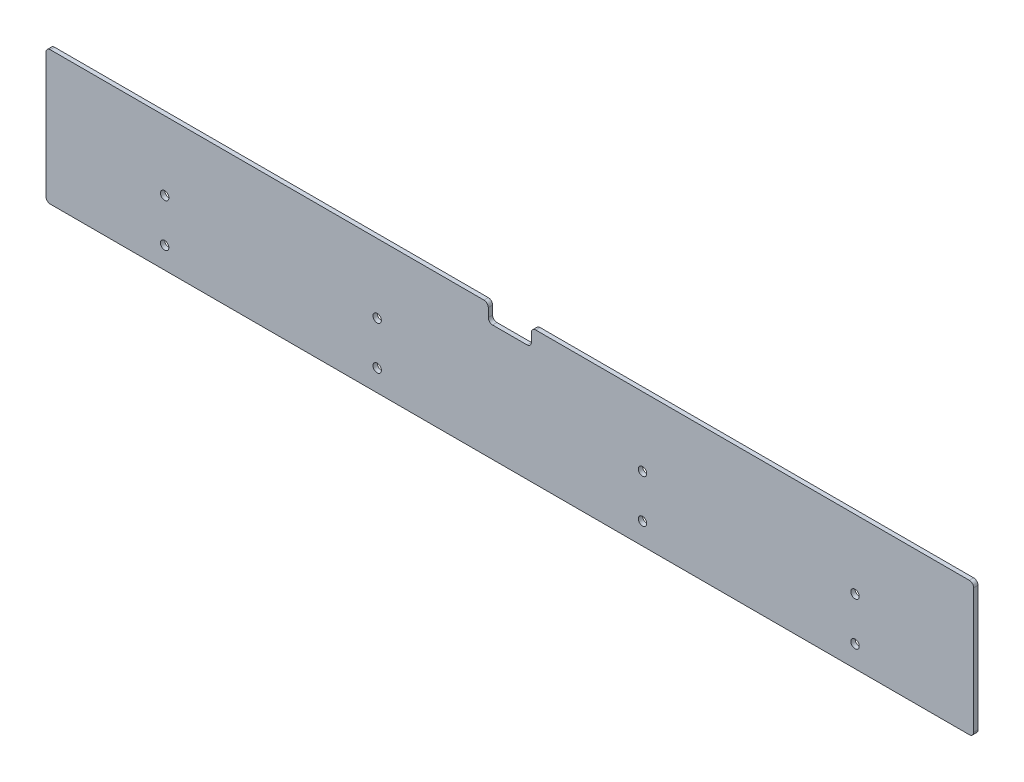
SolidWorks part; units mm, degrees
ref_plane "Front Plane" through (0, 0, 0) normal (0, 0, 1) x (1, 0, 0)
ref_plane "Top Plane" through (0, 0, 0) normal (0, 1, 0) x (1, 0, 0)
ref_plane "Right Plane" through (0, 0, 0) normal (1, 0, 0) x (0, 0, -1)
sketch "Sketch1" plane through (0, 0, 0) normal (0, 0, 1) x (1, 0, 0)
  line L0 (-131.9059, 17.7035) -> (73.0941, 17.7035)
  line L1 (-356.9059, 17.7035) -> (-151.9059, 17.7035)
  line L2 (-356.9059, 17.7035) -> (-356.9059, -44.2965)
  line L3 (-356.9059, -44.2965) -> (73.0941, -44.2965)
  line L4 (73.0941, 17.7035) -> (73.0941, -44.2965)
  line L6 (-151.9059, 17.7035) -> (-151.9059, 9.7035)
  line L7 (-151.9059, 9.7035) -> (-131.9059, 9.7035)
  line L8 (-131.9059, 17.7035) -> (-131.9059, 9.7035)
  circle A0 centre (-80.4059, -14.2965) radius 1.95
  circle A1 centre (-80.4059, -34.2965) radius 1.95
  circle A2 centre (-203.4059, -14.2965) radius 1.95
  circle A3 centre (-203.4059, -34.2965) radius 1.95
  dimension "D3" = 123
  dimension "D4" = 20
  dimension "D1" = 430
  dimension "D2" = 62
  dimension "D5" = 10
  dimension "D6" = 153.5
  dimension "D7" = 20
  dimension "D8" = 8
  dimension "D9" = 205
extrude "Boss-Extrude1" add sketch "Sketch1" along normal blind 2
fillet "Fillet1" radius 2 8 edges at (73.0941, -44.2965, 1) (-356.9059, -44.2965, 1) (-356.9059, 17.7035, 1) (-151.9059, 9.7035, 1) (-151.9059, 17.7035, 1) (-131.9059, 9.7035, 1) (-131.9059, 17.7035, 1) (73.0941, 17.7035, 1)
sketch "Sketch2" plane through (0, 0, 2) normal (0, 0, 1) x (1, 0, 0)
  line L0 (-354.9059, -44.2965) -> (71.0941, -44.2965) construction
  line L1 (-356.9059, 15.7035) -> (-356.9059, -42.2965) construction
  line L2 (73.0941, -42.2965) -> (73.0941, 15.7035) construction
  circle A0 centre (-301.9059, -14.2965) radius 1.95
  circle A1 centre (-301.9059, -34.2965) radius 1.95
  circle A2 centre (18.0941, -14.2965) radius 1.95
  circle A3 centre (18.0941, -34.2965) radius 1.95
  point P14 (0, 0)
  point P15 (0, 0)
  dimension "D1" = 20
  dimension "D2" = 10
  dimension "D3" = 55
  dimension "D4" = 55
  dimension "D5" = 20
  dimension "D6" = 10
extrude "Cut-Extrude1" cut sketch "Sketch2" against normal blind 10
